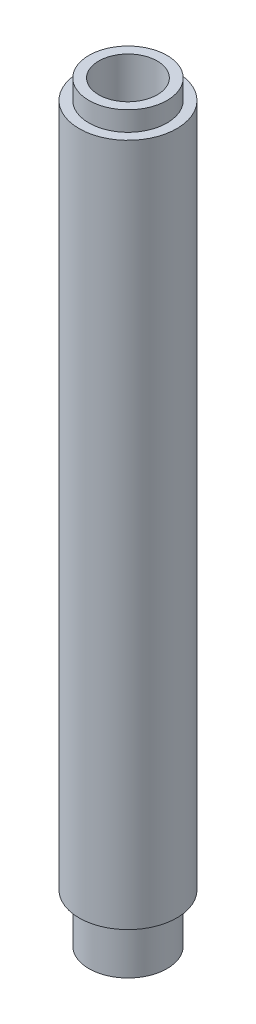
SolidWorks part; units mm, degrees
ref_plane "Front Plane" through (0, 0, 0) normal (0, 0, 1) x (1, 0, 0)
ref_plane "Top Plane" through (0, 0, 0) normal (0, 1, 0) x (1, 0, 0)
ref_plane "Right Plane" through (0, 0, 0) normal (1, 0, 0) x (0, 0, -1)
sketch "Sketch1" plane through (0, 0, 0) normal (0, 1, 0) x (1, 0, 0)
  circle A0 centre (0, 0) radius 12.7
  dimension "D1" = 25.4
extrude "Boss-Extrude1" add sketch "Sketch1" along normal blind 177.8
sketch "Sketch4" plane through (0, 177.8, 0) normal (0, 1, 0) x (1, 0, 0)
  circle A2 centre (0, 0) radius 10.16
  circle A3 centre (0, 0) radius 10.16
  dimension "D1" = 2.54
extrude "Boss-Extrude2" add sketch "Sketch4" along normal blind 5.08
sketch "Sketch5" plane through (0, 182.88, 0) normal (0, 1, 0) x (1, 0, 0)
  circle A0 centre (0, 0) radius 10.16 construction
  circle A1 centre (0, 0) radius 10.16 construction
  circle A2 centre (0, 0) radius 7.62
  dimension "D1" = 2.54
extrude "Cut-Extrude1" cut sketch "Sketch5" against normal through all
sketch "Sketch6" plane through (0, 0, 0) normal (0, -1, 0) x (1, 0, 0)
  circle A0 centre (0, 0) radius 10.16
  circle A1 centre (0, 0) radius 7.62 construction
  circle A2 centre (0, 0) radius 7.62
  dimension "D1" = 20.32
extrude "Boss-Extrude3" add sketch "Sketch6" along normal blind 12.7
